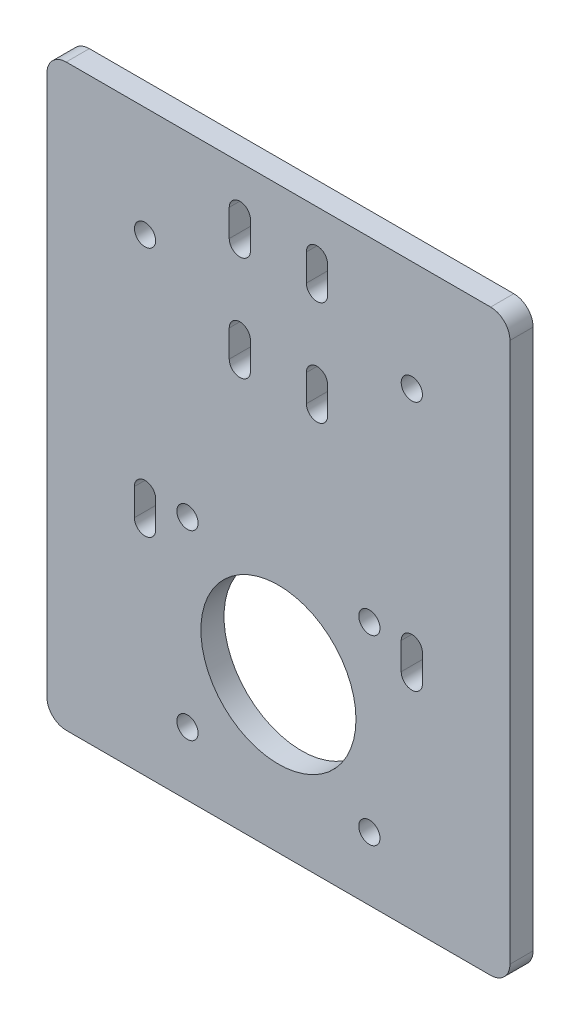
SolidWorks part; units mm, degrees
ref_plane "Front Plane" through (0, 0, 0) normal (0, 0, 1) x (1, 0, 0)
ref_plane "Top Plane" through (0, 0, 0) normal (0, 1, 0) x (1, 0, 0)
ref_plane "Right Plane" through (0, 0, 0) normal (1, 0, 0) x (0, 0, -1)
sketch "Sketch3" plane through (0, 0, 0) normal (0, 0, 1) x (1, 0, 0)
  line L1 (-55, -75) -> (55, -75)
  line L2 (-60, -70) -> (-60, 70)
  line L3 (-55, 75) -> (55, 75)
  line L4 (60, -70) -> (60, 70)
  line L5 (-60, -75) -> (60, 75) construction
  line L6 (-60, 75) -> (60, -75) construction
  arc A0 (-55, -75) -> (-60, -70) centre (-55, -70) cw
  arc A1 (55, -75) -> (60, -70) centre (55, -70) ccw
  arc A2 (55, 75) -> (60, 70) centre (55, 70) cw
  arc A3 (-60, 70) -> (-55, 75) centre (-55, 70) cw
  point P0 (0, 0)
  dimension "D3" = 5
  dimension "D1" = 120
  dimension "D2" = 150
extrude "Boss-Extrude1" add sketch "Sketch3" along normal blind 6
sketch "Sketch4" plane through (0, 0, 6) normal (0, 0, 1) x (1, 0, 0)
  line L0 (-55, -75) -> (55, -75) construction
  circle A0 centre (0, -35) radius 20.1
  dimension "D1" = 40.2
  dimension "D2" = 40
extrude "Cut-Extrude1" cut sketch "Sketch4" against normal blind 6
hole_wizard "M5 Clearance Hole1" positions "Sketch5" profile "Sketch6" hole size "M5" standard "ANSI Metric" end condition through all
sketch "Sketch5" plane through (0, 0, 6) normal (0, 0, 1) x (1, 0, 0)
  circle A0 centre (0, -35) radius 20.1 construction
  point P0 (-23.57, -11.43)
  point P2 (23.57, -11.43)
  point P4 (23.57, -58.57)
  point P6 (-23.57, -58.57)
  dimension "D2" = 23.57
  dimension "D3" = 23.57
  dimension "D5" = 23.57
  dimension "D1" = 47.14
  dimension "D4" = 23.57
sketch "Sketch6" plane through (-23.57, -11.43, 6) normal (1, 0, 0) x (0, -1, 0)
  line L0 (0, 0) -> (0, 6)
  line L1 (0, 6) -> (2.75, 6)
  line L2 (2.75, 6) -> (2.75, 0)
  line L5 (2.75, 0) -> (0, 0)
  line L11 (0, -6.35) -> (0, 107.95) construction
  dimension "Thru Hole Dia." = 5.5
  dimension "Thru Hole Depth" = 6
sketch "Sketch7" plane through (0, 0, 6) normal (0, 0, 1) x (1, 0, 0)
  line L0 (-34.57, -11.43) -> (-34.57, -18.43) construction
  line L1 (-31.82, -11.43) -> (-31.82, -18.43)
  line L2 (-37.32, -11.43) -> (-37.32, -18.43)
  line L3 (0, 37.3663) -> (0, -85.73) construction
  line L4 (34.57, -11.43) -> (34.57, -18.43) construction
  line L5 (31.82, -11.43) -> (31.82, -18.43)
  line L6 (37.32, -11.43) -> (37.32, -18.43)
  arc A0 (-31.82, -11.43) -> (-37.32, -11.43) centre (-34.57, -11.43) ccw
  arc A1 (-37.32, -18.43) -> (-31.82, -18.43) centre (-34.57, -18.43) ccw
  circle A2 centre (-23.57, -11.43) radius 2.75 construction
  arc A3 (31.82, -11.43) -> (37.32, -11.43) centre (34.57, -11.43) cw
  arc A4 (37.32, -18.43) -> (31.82, -18.43) centre (34.57, -18.43) cw
  point P2 (-34.57, -14.93)
  point P11 (34.57, -14.93)
  dimension "D1" = 2.75
  dimension "D2" = 7
  dimension "D3" = 11
extrude "Cut-Extrude2" cut sketch "Sketch7" against normal blind 6
hole_wizard "M5 Clearance Hole2" positions "Sketch8" profile "Sketch9" hole size "M5" standard "ANSI Metric" end condition through all
sketch "Sketch8" plane through (0, 0, 6) normal (0, 0, 1) x (1, 0, 0)
  point P0 (-34.57, 46.47)
  point P2 (34.57, 46.47)
  dimension "D1" = 61.4
sketch "Sketch9" plane through (-34.57, 46.47, 6) normal (1, 0, 0) x (0, -1, 0)
  line L0 (0, 0) -> (0, 6)
  line L1 (0, 6) -> (2.75, 6)
  line L2 (2.75, 6) -> (2.75, 0)
  line L5 (2.75, 0) -> (0, 0)
  line L11 (0, -6.35) -> (0, 107.95) construction
  dimension "Thru Hole Dia." = 5.5
  dimension "Thru Hole Depth" = 6
sketch "Sketch10" plane through (0, 0, 6) normal (0, 0, 1) x (1, 0, 0)
  line L0 (-10, 63.5) -> (-10, 56.5) construction
  line L1 (-7.25, 63.5) -> (-7.25, 56.5)
  line L2 (-12.75, 63.5) -> (-12.75, 56.5)
  line L3 (10, 63.5) -> (10, 56.5) construction
  line L4 (12.75, 63.5) -> (12.75, 56.5)
  line L5 (7.25, 63.5) -> (7.25, 56.5)
  line L6 (55, 75) -> (-55, 75) construction
  line L7 (34.57, 46.47) -> (-34.57, 46.47) construction
  line L8 (0, 37.3663) -> (0, -85.73) construction
  line L9 (-10, 29.44) -> (-10, 36.44) construction
  line L10 (-7.25, 29.44) -> (-7.25, 36.44)
  line L11 (-12.75, 29.44) -> (-12.75, 36.44)
  line L12 (10, 29.44) -> (10, 36.44) construction
  line L13 (12.75, 29.44) -> (12.75, 36.44)
  line L14 (7.25, 29.44) -> (7.25, 36.44)
  arc A0 (-7.25, 63.5) -> (-12.75, 63.5) centre (-10, 63.5) ccw
  arc A1 (-12.75, 56.5) -> (-7.25, 56.5) centre (-10, 56.5) ccw
  arc A2 (12.75, 63.5) -> (7.25, 63.5) centre (10, 63.5) ccw
  arc A3 (7.25, 56.5) -> (12.75, 56.5) centre (10, 56.5) ccw
  arc A4 (-7.25, 29.44) -> (-12.75, 29.44) centre (-10, 29.44) cw
  arc A5 (-12.75, 36.44) -> (-7.25, 36.44) centre (-10, 36.44) cw
  arc A6 (12.75, 29.44) -> (7.25, 29.44) centre (10, 29.44) cw
  arc A7 (7.25, 36.44) -> (12.75, 36.44) centre (10, 36.44) cw
  point P2 (-10, 60)
  point P7 (10, 60)
  point P28 (-10, 32.94)
  point P35 (10, 32.94)
  dimension "D1" = 2.75
  dimension "D2" = 7
  dimension "D3" = 15
  dimension "D4" = 20
  dimension "D5" = 10
extrude "Cut-Extrude3" cut sketch "Sketch10" against normal blind 6
sketch "Sketch11" plane through (0, 0, 0) normal (0, 0, -1) x (-1, 0, 0)
  line L0 (-41.0184, 46.47) -> (71.6367, 46.47) construction
